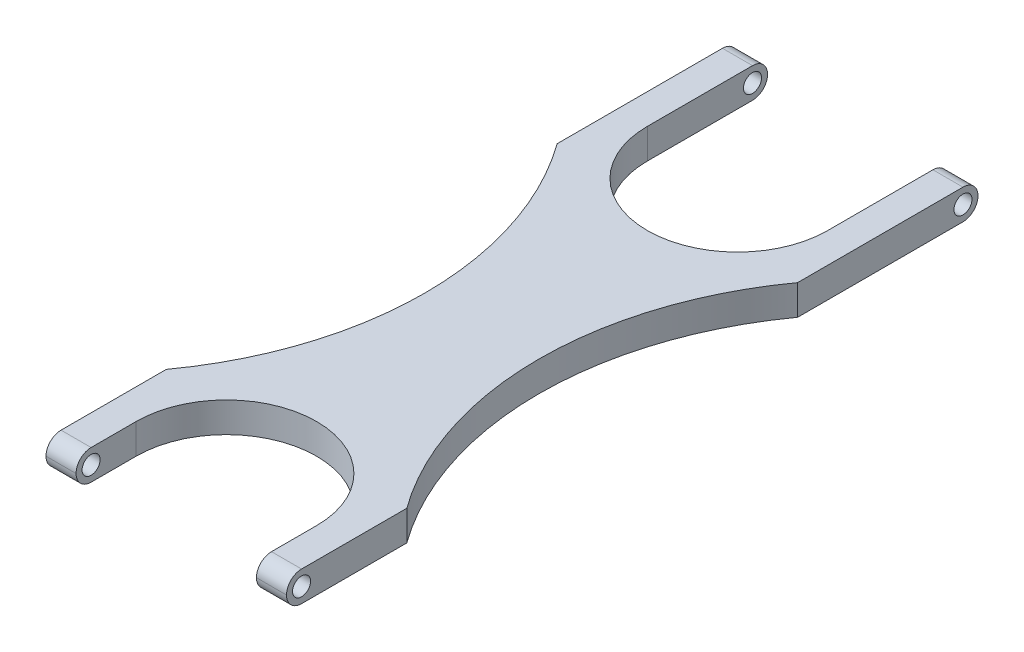
SolidWorks part; units mm, degrees
ref_plane "Front Plane" through (0, 0, 0) normal (0, 0, 1) x (1, 0, 0)
ref_plane "Top Plane" through (0, 0, 0) normal (0, 1, 0) x (1, 0, 0)
ref_plane "Right Plane" through (0, 0, 0) normal (1, 0, 0) x (0, 0, -1)
sketch "Sketch1" plane through (0, 0, 0) normal (0, 1, 0) x (1, 0, 0)
  line L0 (0, 0) -> (12.7, 0)
  line L1 (12.7, 0) -> (12.7, -50.8)
  line L2 (0, 0) -> (0, -76.2)
  line L3 (0, -241.3) -> (0, -292.1)
  line L4 (0, -292.1) -> (12.7, -292.1)
  line L5 (12.7, -292.1) -> (12.7, -266.7)
  line L6 (50.8, -88.9) -> (50.8, -228.6) construction
  line L7 (88.9, -292.1) -> (88.9, -266.7)
  line L8 (101.6, -292.1) -> (88.9, -292.1)
  line L9 (101.6, -241.3) -> (101.6, -292.1)
  line L10 (101.6, 0) -> (101.6, -76.2)
  line L11 (88.9, 0) -> (88.9, -50.8)
  line L12 (101.6, 0) -> (88.9, 0)
  arc A0 (12.7, -50.8) -> (50.8, -88.9) centre (50.8, -50.8) ccw
  arc A1 (0, -76.2) -> (0, -241.3) centre (-114.3, -158.75) cw
  arc A2 (12.7, -266.7) -> (50.8, -228.6) centre (50.8, -266.7) cw
  arc A3 (88.9, -266.7) -> (50.8, -228.6) centre (50.8, -266.7) ccw
  arc A4 (88.9, -50.8) -> (50.8, -88.9) centre (50.8, -50.8) cw
  arc A5 (101.6, -76.2) -> (101.6, -241.3) centre (215.9, -158.75) ccw
  dimension "D8" = 330.2
  dimension "D1" = 292.1
  dimension "D2" = 12.7
  dimension "D3" = 76.2
  dimension "D4" = 50.8
  dimension "D5" = 25.4
  dimension "D6" = 76.2
  dimension "D7" = 50.8
extrude "Boss-Extrude1" add sketch "Sketch1" along normal blind 12.7
fillet "Fillet1" radius 6.35 8 edges at (95.25, 0, 0) (6.35, 0, 0) (95.25, 12.7, 0) (6.35, 12.7, 0) (6.35, 0, 292.1) (6.35, 12.7, 292.1) (95.25, 0, 292.1) (95.25, 12.7, 292.1)
sketch "Sketch2" plane through (101.6, 0, 0) normal (1, 0, 0) x (0, 0, -1)
  circle A0 centre (-285.75, 6.35) radius 3.81
extrude "Cut-Extrude1" cut sketch "Sketch2" against normal through all
sketch "Sketch3" plane through (101.6, 0, 0) normal (1, 0, 0) x (0, 0, -1)
  circle A0 centre (-6.35, 6.35) radius 3.81
extrude "Cut-Extrude2" cut sketch "Sketch3" against normal through all
